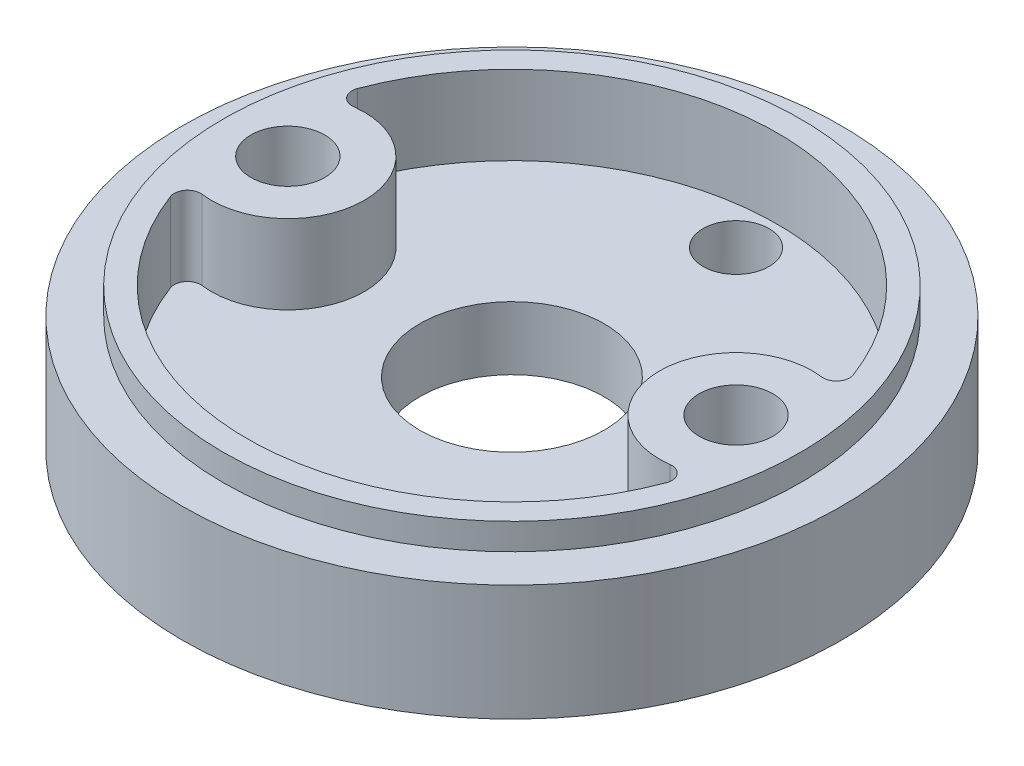
SolidWorks part; units mm, degrees
material "6061-T6 (SS)"
ref_plane "Front Plane" through (0, 0, 0) normal (0, 0, 1) x (1, 0, 0)
ref_plane "Top Plane" through (0, 0, 0) normal (0, 1, 0) x (1, 0, 0)
ref_plane "Right Plane" through (0, 0, 0) normal (1, 0, 0) x (0, 0, -1)
sketch "Sketch1" plane through (0, 0, 0) normal (0, 1, 0) x (1, 0, 0)
  circle A0 centre (0, 0) radius 12.5
  dimension "D1" = 25
extrude "Boss-Extrude1" add sketch "Sketch1" along normal blind 4.4
sketch "Sketch2" plane through (0, 4.4, 0) normal (0, 1, 0) x (1, 0, 0)
  circle A0 centre (0, 0) radius 10.95
  dimension "D1" = 21.9
extrude "Boss-Extrude2" add sketch "Sketch2" along normal blind 1
sketch "Sketch3" plane through (0, 5.4, 0) normal (0, 1, 0) x (1, 0, 0)
  circle A0 centre (0, 0) radius 10.05
  circle A1 centre (0, 0) radius 10.95 construction
  dimension "D1" = 0.9
extrude "Cut-Extrude1" cut sketch "Sketch3" against normal blind 3
sketch "Sketch4" plane through (0, 2.4, 0) normal (0, 1, 0) x (1, 0, 0)
  circle A0 centre (0, 0) radius 3.5
  dimension "D1" = 7
extrude "Cut-Extrude2" cut sketch "Sketch4" against normal through all
sketch "Sketch5" plane through (0, 0, 0) normal (0, -1, 0) x (1, 0, 0)
  line L0 (-8.5, 0) -> (8.5, 0) construction
  circle A0 centre (-8.5, 0) radius 1.4
  circle A1 centre (8.5, 0) radius 1.4
  dimension "D2" = 2.8
  dimension "D1" = 17
extrude "Cut-Extrude3" cut sketch "Sketch5" against normal through all
sketch "Sketch6" plane through (0, 2.4, 0) normal (0, 1, 0) x (1, 0, 0)
  circle A0 centre (8.5, 0) radius 1.4 construction
  circle A1 centre (-8.5, 0) radius 1.4 construction
  circle A2 centre (8.5, 0) radius 1.4
  circle A3 centre (-8.5, 0) radius 1.4
  arc A4 (-9.6966, 2.6416) -> (-9.6966, -2.6416) centre (-8.5, 0) cw
  circle A5 centre (0, 0) radius 10.05 construction
  arc A6 (9.6966, -2.6416) -> (9.6966, 2.6416) centre (8.5, 0) cw
  arc A7 (-9.6966, 2.6416) -> (-9.6966, -2.6416) centre (0, 0) ccw
  arc A8 (9.6966, 2.6416) -> (9.6966, -2.6416) centre (0, 0) cw
  circle A9 centre (0, 0) radius 10.05 construction
  dimension "D1" = 1.5
extrude "Boss-Extrude3" add sketch "Sketch6" along normal up to surface (3 mm away) up to face at (0, 5.4, 10.05)
fillet "Fillet1" radius 0.5 4 edges at (9.6966, 3.9, 2.6416) (9.6966, 3.9, -2.6416) (-9.6966, 3.9, -2.6416) (-9.6966, 3.9, 2.6416)
sketch "Sketch7" plane through (0, 0, 0) normal (0, -1, 0) x (1, 0, 0)
  circle A0 centre (-8.5, 0) radius 2.5
  circle A1 centre (8.5, 0) radius 2.5
  dimension "D1" = 5
extrude "Cut-Extrude4" cut sketch "Sketch7" against normal blind 2.65
sketch "Sketch8" plane through (0, 0, 0) normal (0, -1, 0) x (1, 0, 0)
  line L0 (0, 8.5) -> (0, -8.5) construction
  point P3 (0, 8.5)
  point P5 (0, -8.5)
  dimension "D1" = 17
hole_wizard "M3x0.5 Tapped Hole1" positions "Sketch9" profile "Sketch10" tap size "M3x0.5" standard "ANSI Metric" end condition through all
sketch "Sketch9" plane through (0, 0, 0) normal (0, -1, 0) x (-1, 0, 0)
  point P0 (0, 8.5)
  point P3 (0, -8.5)
sketch "Sketch10" plane through (0, 0, -8.5) normal (1, 0, 0) x (0, 0, -1)
  line L0 (0, 0) -> (0, 5.4)
  line L1 (0, 5.4) -> (1.25, 5.4)
  line L2 (1.25, 5.4) -> (1.25, 0)
  line L5 (1.25, 0) -> (0, 0)
  line L11 (0, -6.35) -> (0, 107.95) construction
  dimension "Thru Tap Drill Dia." = 2.5
  dimension "Thru Tap Drill Depth" = 5.4
cosmetic thread "Hole Thread1" parameters "D2"=3
cosmetic thread "Hole Thread2" parameters "D2"=3
